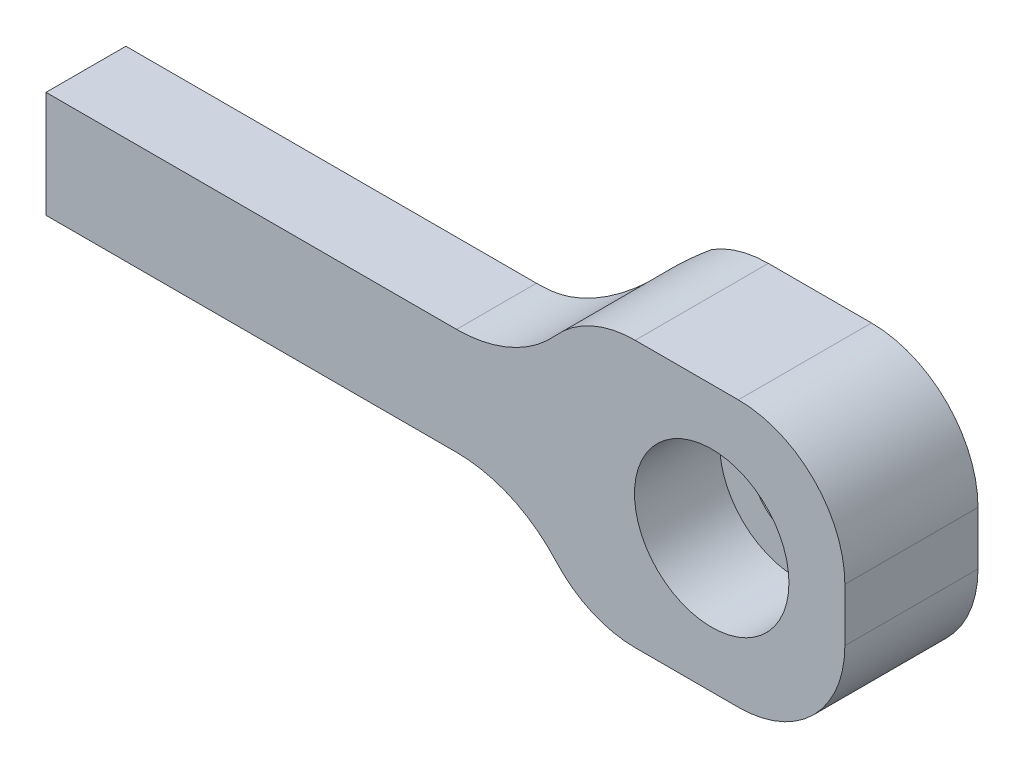
SolidWorks part; units mm, degrees
ref_plane "Front Plane" through (0, 0, 0) normal (0, 0, 1) x (1, 0, 0)
ref_plane "Top Plane" through (0, 0, 0) normal (0, 1, 0) x (1, 0, 0)
ref_plane "Right Plane" through (0, 0, 0) normal (1, 0, 0) x (0, 0, -1)
sketch "Sketch1" plane through (0, 0, 0) normal (0, 0, 1) x (1, 0, 0)
  line L1 (-31.75, -6.35) -> (6.35, -6.35)
  line L2 (-31.75, -6.35) -> (-31.75, 6.35)
  line L3 (-31.75, 6.35) -> (6.35, 6.35)
  line L4 (6.35, -6.35) -> (6.35, 6.35)
  line L5 (-31.75, -6.35) -> (6.35, 6.35) construction
  line L6 (-31.75, 6.35) -> (6.35, -6.35) construction
  point P0 (0, 0)
  point P6 (0, 0)
  point P7 (0, 0)
  dimension "D1" = 38.1
  dimension "D2" = 12.7
  dimension "D3" = 6.35
  dimension "D4" = 6.35
extrude "Boss-Extrude1" add sketch "Sketch1" along normal blind 6.35
sketch "Sketch2" plane through (0, 0, 6.35) normal (0, 0, 1) x (1, 0, 0)
  circle A0 centre (0, 0) radius 2.159
  dimension "D1" = 4.318
extrude "Cut-Extrude1" cut sketch "Sketch2" against normal through all
sketch "Sketch3" plane through (0, 0, 6.35) normal (0, 0, 1) x (1, 0, 0)
  circle A0 centre (0, 0) radius 3.683
  dimension "D1" = 7.366
extrude "Cut-Extrude2" cut sketch "Sketch3" against normal blind 4.064
sketch "Sketch5" plane through (0, 0, 6.35) normal (0, 0, 1) x (1, 0, 0)
  line L1 (-31.75, 6.35) -> (-6.35, 6.35)
  line L2 (-31.75, 6.35) -> (-31.75, 2.54)
  line L3 (-31.75, 2.54) -> (-6.35, 2.54)
  line L4 (-6.35, 6.35) -> (-6.35, 2.54)
  line L5 (-31.75, -6.35) -> (-6.35, -6.35)
  line L6 (-31.75, -6.35) -> (-31.75, -2.54)
  line L7 (-31.75, -2.54) -> (-6.35, -2.54)
  line L8 (-6.35, -6.35) -> (-6.35, -2.54)
  dimension "D1" = 3.81
  dimension "D2" = 25.4
extrude "Cut-Extrude3" cut sketch "Sketch5" against normal through all
sketch "Sketch6" plane through (0, 2.54, 0) normal (0, 1, 0) x (1, 0, 0)
  line L0 (-6.35, 0) -> (-6.35, -6.35) construction
  line L1 (-31.75, 0) -> (-6.35, 0)
  line L2 (-31.75, 0) -> (-31.75, -2.54)
  line L3 (-31.75, -2.54) -> (-6.35, -2.54)
  line L4 (-6.35, 0) -> (-6.35, -2.54)
  dimension "D1" = 2.54
extrude "Cut-Extrude4" cut sketch "Sketch6" against normal through all
fillet "Fillet3" radius 6.35 3 edges at (-6.35, -2.54, 4.445) (-6.35, 0, 2.54) (-6.35, 2.54, 4.445)
fillet "Fillet4" radius 5.08 4 edges at (-6.35, -6.35, 3.175) (6.35, 6.35, 3.175) (-6.35, 6.35, 3.175) (6.35, -6.35, 3.175)
